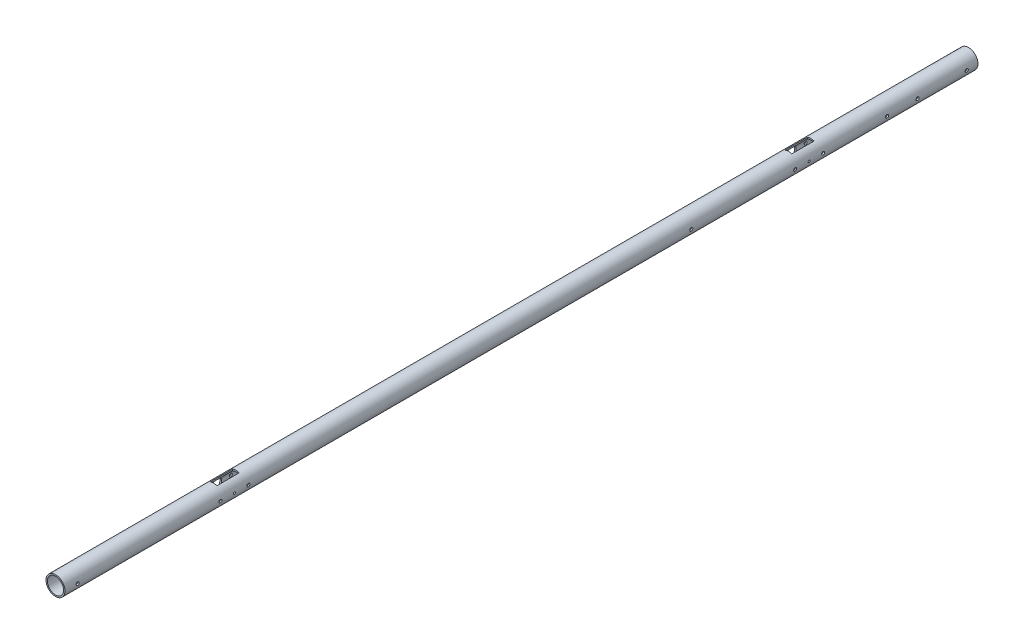
SolidWorks part; units mm, degrees
ref_plane "Front" through (0, 0, 0) normal (0, 0, 1) x (1, 0, 0)
ref_plane "Top" through (0, 0, 0) normal (0, 1, 0) x (1, 0, 0)
ref_plane "Right" through (0, 0, 0) normal (1, 0, 0) x (0, 0, -1)
sketch "Sketch1" plane through (0, 0, 0) normal (0, 0, 1) x (1, 0, 0)
  circle A0 centre (0, 0) radius 9.36
  circle A1 centre (0, 0) radius 7.99
extrude "Extrude1" add sketch "Sketch1" along normal blind 900
sketch "Sketch4" plane through (0, 0, 0) normal (1, 0, 0) x (0, 0, -1)
  line L0 (-900, 0) -> (0, 0) construction
  circle A0 centre (-166.425, 0) radius 1
  circle A1 centre (-733, 0) radius 1
  circle A2 centre (-282.57, 0) radius 1.5
extrude "Cut-Extrude3" cut sketch "Sketch4" along normal through all
sketch "Sketch5" plane through (0, 0, 0) normal (1, 0, 0) x (0, 0, -1)
  line L0 (-900, 0) -> (0, 0) construction
  line L1 (-900, 0) -> (0, 0) construction
  circle A0 centre (-166.425, 0) radius 4.5
  circle A1 centre (-733, 0) radius 4.5
extrude "Cut-Extrude6" cut sketch "Sketch5" against normal through all
sketch "Sketch6" plane through (0, 0, 0) normal (0, 1, 0) x (1, 0, 0)
  line L1 (-3.5, -155.425) -> (3.175, -155.425)
  line L2 (-3.5, -155.425) -> (-3.5, -177.425)
  line L3 (-3.5, -177.425) -> (3.175, -177.425)
  line L4 (3.175, -155.425) -> (3.175, -177.425)
  line L5 (-3.5, -722) -> (3.175, -722)
  line L6 (-3.5, -722) -> (-3.5, -744)
  line L7 (-3.5, -744) -> (3.175, -744)
  line L8 (3.175, -722) -> (3.175, -744)
extrude "Cut-Extrude7" cut sketch "Sketch6" along normal through all
sketch "Sketch7" plane through (0, 0, 0) normal (0, 1, 0) x (1, 0, 0)
  line L0 (-3.5, -155.425) -> (-3.5, -177.425) construction
  line L1 (-3.5, -158.425) -> (3.175, -158.425)
  line L2 (-3.5, -158.425) -> (-3.5, -174.425)
  line L3 (-3.5, -174.425) -> (3.175, -174.425)
  line L4 (3.175, -158.425) -> (3.175, -174.425)
  line L5 (3.175, -744) -> (3.175, -722) construction
  line L6 (-3.5, -725) -> (3.175, -725)
  line L7 (-3.5, -725) -> (-3.5, -741)
  line L8 (-3.5, -741) -> (3.175, -741)
  line L9 (3.175, -725) -> (3.175, -741)
extrude "Cut-Extrude8" cut sketch "Sketch7" against normal through all
sketch "Sketch8" plane through (0, 0, 0) normal (1, 0, 0) x (0, 0, -1)
  line L0 (-741, 0) -> (-725, 0) construction
  line L1 (-741, 0) -> (-725, 0) construction
  line L2 (-741, 0) -> (-725, 0) construction
  circle A0 centre (-152.6138, 0) radius 1.5
  circle A1 centre (-180.1763, 0) radius 1.5
  circle A2 centre (-59.48, 0) radius 1.55
  circle A3 centre (-89.64, 0) radius 1.55
  circle A4 centre (-11.11, 0) radius 1.55
  circle A5 centre (-746.7513, 0) radius 1.5
  circle A6 centre (-719.1888, 0) radius 1.5
  circle A7 centre (-887.4125, 0) radius 1.5
extrude "Cut-Extrude9" cut sketch "Sketch8" against normal through all and the other way through all
sketch "Sketch9" plane through (0, 0, 0) normal (0, 1, 0) x (1, 0, 0)
  line L1 (-6.36, -19.19) -> (-12.5, -19.19)
  line L2 (-6.36, -19.19) -> (-6.36, -52.69)
  line L3 (-6.36, -52.69) -> (-12.5, -52.69)
  line L4 (-12.5, -19.19) -> (-12.5, -52.69)
extrude "Cut-Extrude10" cut sketch "Sketch9" against normal through all and the other way through all
